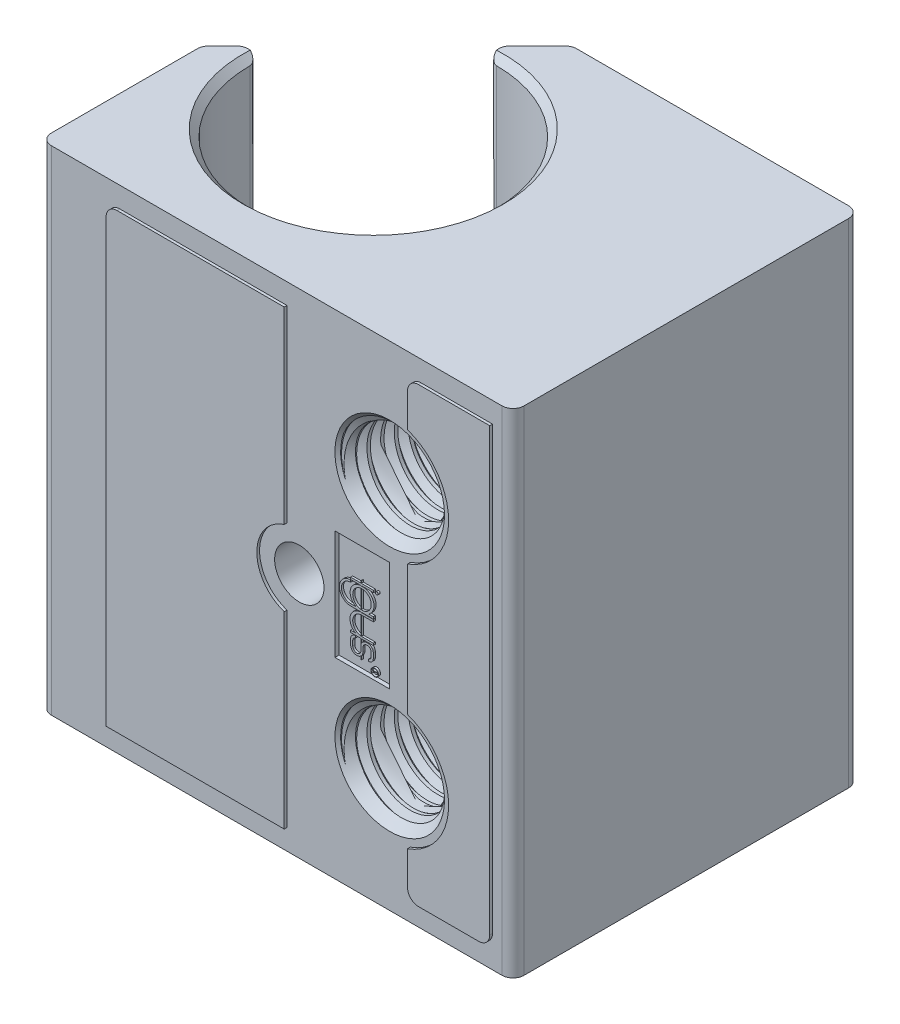
SolidWorks part; units mm, degrees
ref_plane "Front Plane" through (0, 0, 0) normal (0, 0, 1) x (1, 0, 0)
ref_plane "Top Plane" through (0, 0, 0) normal (0, 1, 0) x (1, 0, 0)
ref_plane "Right Plane" through (0, 0, 0) normal (1, 0, 0) x (0, 0, -1)
ref_plane "Plane1" through (0, 80.199, 0) normal (0, 1, 0) x (1, 0, 0)
sketch "Sketch1" plane through (0, 80.199, 0) normal (0, 1, 0) x (1, 0, 0)
  line L0 (28.5, 31) -> (28.5, 29.9861)
  line L1 (20.0139, 21.5) -> (19, 21.5)
  line L2 (19, 21.5) -> (17.5, 20)
  line L3 (17.5, 20) -> (17.5, 8.2)
  line L4 (17.5, 8.2) -> (52, 8.2)
  line L5 (52, 8.2) -> (52, 33.5)
  line L6 (52, 33.5) -> (31, 33.5)
  line L7 (31, 33.5) -> (28.5, 31)
  arc A0 (28.5, 29.9861) -> (20.0139, 21.5) centre (29, 21) cw
extrude "Boss-Extrude1" add sketch "Sketch1" against normal blind 16.2
sketch "Sketch2" plane through (0, 80.199, 0) normal (0, 1, 0) x (-1, 0, 0)
  line L0 (-28.5, -30.9875) -> (-28.5, -31)
  line L1 (-28.5, -31) -> (-31, -33.5)
  line L2 (-31, -33.5) -> (-52, -33.5)
  line L3 (-52, -33.5) -> (-52, -8.2)
  line L4 (-52, -8.2) -> (-17.5, -8.2)
  line L5 (-17.5, -8.2) -> (-17.5, -20)
  line L6 (-17.5, -20) -> (-19, -21.5)
  line L7 (-19, -21.5) -> (-19.0125, -21.5)
  arc A0 (-19.0125, -21.5) -> (-28.5, -30.9875) centre (-29, -21) ccw
extrude "Boss-Extrude2" add sketch "Sketch2" along normal blind 3.6
sketch "Sketch3" plane through (0, 83.799, 0) normal (0, 1, 0) x (-1, 0, 0)
  line L0 (-28.5, -21.5) -> (-28.5, -31)
  line L1 (-28.5, -31) -> (-31, -33.5)
  line L2 (-31, -33.5) -> (-52, -33.5)
  line L3 (-52, -33.5) -> (-52, -8.2)
  line L4 (-52, -8.2) -> (-17.5, -8.2)
  line L5 (-17.5, -8.2) -> (-17.5, -20)
  line L6 (-17.5, -20) -> (-19, -21.5)
  line L7 (-19, -21.5) -> (-28.5, -21.5)
extrude "Boss-Extrude3" add sketch "Sketch3" along normal blind 16.2
hole_wizard "Hole1" positions "Sketch5" profile "Sketch4" legacy
sketch "Sketch5" plane through (0, 83.799, 0) normal (0, -1, 0) x (-1, 0, 0)
  point P0 (-29, 21)
sketch "Sketch4" plane through (29, 83.799, -21) normal (1, 0, 0) x (0, 0, -1)
  line L0 (0, 0) -> (0, 16.2)
  line L1 (0, 16.2) -> (9, 16.2)
  line L2 (9, 16.2) -> (9, 0)
  line L3 (9, 0) -> (0, 0)
  line L4 (0, 110) -> (0, -10) construction
  dimension "Diameter" = 18
  dimension "Depth" = 16.2
sketch "Sketch6" plane through (0, 0, -8.2) normal (0, 0, 1) x (1, 0, 0)
  line L0 (44.5, 98.499) -> (50.5, 98.499)
  line L1 (50.5, 98.499) -> (50.5, 65.499)
  line L2 (50.5, 65.499) -> (44.5, 65.499)
  line L3 (44.5, 65.499) -> (44.5, 68.7564)
  line L4 (44.5, 77.2416) -> (44.5, 86.7564)
  line L5 (44.5, 95.2416) -> (44.5, 98.499)
  arc A0 (44.5, 68.7564) -> (44.5, 77.2416) centre (43, 72.999) ccw
  arc A1 (44.5, 86.7564) -> (44.5, 95.2416) centre (43, 90.999) ccw
extrude "Boss-Extrude4" add sketch "Sketch6" along normal blind 0.2
sketch "Sketch7" plane through (0, 0, -8.2) normal (0, 0, 1) x (1, 0, 0)
  line L0 (35.5, 65.499) -> (22.5, 65.499)
  line L1 (22.5, 65.499) -> (22.5, 98.499)
  line L2 (22.5, 98.499) -> (35.5, 98.499)
  line L3 (35.5, 98.499) -> (35.5, 84.7558)
  line L4 (35.5, 79.2422) -> (35.5, 65.499)
  arc A0 (35.5, 84.7558) -> (35.5, 79.2422) centre (36.4, 81.999) ccw
extrude "Boss-Extrude5" add sketch "Sketch7" along normal blind 0.2
sketch "Sketch8" plane through (0, 0, -8.2) normal (0, 0, 1) x (1, 0, 0)
  line L0 (39, 77.999) -> (43, 77.999)
  line L1 (43, 77.999) -> (43, 85.999)
  line L2 (43, 85.999) -> (39, 85.999)
  line L3 (39, 85.999) -> (39, 77.999)
extrude "Cut-Extrude1" cut sketch "Sketch8" against normal blind 0.3
sketch "Sketch9" plane through (0, 0, -8.5) normal (0, 0, 1) x (1, 0, 0)
  circle A0 centre (41.75, 78.349) radius 0.275
extrude "Boss-Extrude6" add sketch "Sketch9" along normal blind 0.15
hole_wizard "Hole2" positions "Sketch11" profile "Sketch10" legacy
sketch "Sketch11" plane through (0, 0, -8.35) normal (0, 0, 1) x (1, 0, 0)
  point P0 (41.75, 78.349)
sketch "Sketch10" plane through (41.75, 78.349, -8.35) normal (1, 0, 0) x (0, -1, 0)
  line L0 (0, 0) -> (0, 25.15)
  line L1 (0, 25.15) -> (0.25, 25.15)
  line L2 (0.25, 25.15) -> (0.25, 0)
  line L3 (0.25, 0) -> (0, 0)
  line L4 (0, 110) -> (0, -10) construction
  dimension "Diameter" = 0.5
  dimension "Depth" = 25.15
ref_plane "Plane2" through (0, 0, -8.5) normal (0, 0, -1) x (-1, 0, 0)
sketch "Sketch12" plane through (0, 0, -8.5) normal (0, 0, -1) x (-1, 0, 0)
  line L0 (-41.925, 78.424) -> (-41.925, 78.349)
  line L1 (-41.75, 78.349) -> (-41.75, 78.3615)
  line L2 (-41.75, 78.3615) -> (-41.575, 78.2615)
  line L3 (-41.575, 78.2615) -> (-41.5747, 78.3759)
  line L4 (-41.5747, 78.3759) -> (-41.75, 78.3759)
  line L5 (-41.75, 78.3759) -> (-41.75, 78.4115)
  line L6 (-41.75, 78.4115) -> (-41.575, 78.4115)
  line L7 (-41.575, 78.4115) -> (-41.575, 78.424)
  line L8 (-41.575, 78.424) -> (-41.925, 78.424)
  arc A0 (-41.925, 78.349) -> (-41.75, 78.349) centre (-41.8375, 78.349) ccw
extrude "Boss-Extrude7" add sketch "Sketch12" against normal blind 0.15
sketch "Sketch13" plane through (0, 0, -8.35) normal (0, 0, 1) x (1, 0, 0)
  line L0 (41.7625, 78.4115) -> (41.7625, 78.349)
  line L1 (41.9125, 78.349) -> (41.9125, 78.4115)
  line L2 (41.9125, 78.4115) -> (41.7625, 78.4115)
  arc A0 (41.7625, 78.349) -> (41.9125, 78.349) centre (41.8375, 78.349) ccw
extrude "Cut-Extrude2" cut sketch "Sketch13" against normal blind 0.15
sketch "Sketch14" plane through (0, 0, -8.5) normal (0, 0, 1) x (1, 0, 0)
  line L0 (41.65, 80.149) -> (41.65, 79.999)
  line L1 (41.65, 79.999) -> (40.775, 79.999)
  line L2 (40.775, 79.999) -> (40.775, 79.699)
  line L3 (41.65, 79.549) -> (41.65, 79.174)
  line L4 (41.3, 78.824) -> (41.3, 78.974)
  line L5 (41.5, 79.224) -> (41.5, 79.499)
  line L6 (40.9, 79.499) -> (40.9, 79.224)
  line L7 (40.775, 78.9128) -> (40.775, 78.649)
  line L8 (40.775, 78.649) -> (40.75, 78.649)
  line L9 (40.75, 78.649) -> (40.75, 78.8886)
  line L10 (40, 79.224) -> (40, 79.624)
  line L11 (40.35, 79.974) -> (40.35, 79.824)
  line L12 (40.15, 79.574) -> (40.15, 79.224)
  line L13 (40.75, 79.224) -> (40.75, 79.999)
  line L14 (40.75, 79.999) -> (40, 79.999)
  line L15 (40, 79.999) -> (40, 80.149)
  line L16 (40, 80.149) -> (40.35, 80.149)
  line L17 (40.75, 81.649) -> (40.75, 81.674)
  line L18 (40.75, 81.674) -> (40, 81.674)
  line L19 (40, 83.324) -> (40, 83.174)
  line L20 (40, 81.824) -> (40.4, 81.824)
  line L21 (40.75, 83.324) -> (40.75, 83.349)
  line L22 (40.75, 83.349) -> (40, 83.349)
  line L23 (40, 83.349) -> (40, 83.499)
  line L24 (40, 83.499) -> (40.75, 83.499)
  line L25 (40.75, 83.499) -> (40.75, 83.649)
  line L26 (40.75, 83.649) -> (40.775, 83.649)
  line L27 (40.775, 83.649) -> (40.775, 83.499)
  line L28 (40.775, 83.499) -> (41.675, 83.499)
  line L29 (41.675, 83.499) -> (41.675, 83.349)
  line L30 (41.675, 83.349) -> (40.8, 83.349)
  line L31 (40.8, 83.349) -> (40.8, 83.324)
  line L32 (41.3, 81.824) -> (41.65, 81.824)
  line L33 (41.65, 81.824) -> (41.65, 81.674)
  line L34 (41.65, 81.674) -> (40.775, 81.674)
  line L35 (40.775, 81.674) -> (40.775, 81.649)
  line L36 (40.775, 81.649) -> (41.65, 81.649)
  line L37 (41.65, 81.649) -> (41.65, 81.499)
  line L38 (41.65, 81.499) -> (40.775, 81.499)
  line L39 (40.775, 81.499) -> (40.775, 80.1508)
  line L40 (40.825, 80.149) -> (41.65, 80.149)
  arc A0 (40.775, 79.699) -> (41.2, 79.949) centre (41.2, 79.4627) cw
  arc A1 (41.2, 79.949) -> (41.65, 79.549) centre (41.2472, 79.549) cw
  arc A2 (41.65, 79.174) -> (41.3, 78.824) centre (41.3, 79.174) cw
  arc A3 (41.3, 78.974) -> (41.5, 79.224) centre (41.2438, 79.224) ccw
  arc A4 (41.5, 79.499) -> (40.9, 79.499) centre (41.2, 79.499) ccw
  arc A5 (40.9, 79.224) -> (40.775, 78.9128) centre (40.45, 79.224) cw
  arc A6 (40.75, 78.8886) -> (40, 79.224) centre (40.45, 79.224) cw
  arc A7 (40, 79.624) -> (40.35, 79.974) centre (40.35, 79.624) cw
  arc A8 (40.35, 79.824) -> (40.15, 79.574) centre (40.4062, 79.574) ccw
  arc A9 (40.15, 79.224) -> (40.75, 79.224) centre (40.45, 79.224) ccw
  arc A10 (40.35, 80.149) -> (40.75, 81.649) centre (40.75, 80.8457) cw
  arc A11 (40, 81.674) -> (40, 83.324) centre (40, 82.499) cw
  arc A12 (40, 83.174) -> (40, 81.824) centre (40, 82.499) ccw
  arc A13 (40.4, 81.824) -> (40.75, 83.324) centre (40.75, 82.5332) cw
  arc A14 (40.8, 83.324) -> (41.3, 81.824) centre (40.8965, 82.5228) cw
  arc A15 (40.775, 80.1508) -> (40.825, 80.149) centre (40.825, 80.8261) ccw
extrude "Boss-Extrude8" add sketch "Sketch14" along normal blind 0.15
sketch "Sketch15" plane through (0, 0, -8.35) normal (0, 0, 1) x (1, 0, 0)
  line L0 (40.75, 80.1532) -> (40.75, 81.499)
  arc A0 (40.75, 81.499) -> (40.75, 80.1532) centre (40.825, 80.8261) ccw
extrude "Cut-Extrude3" cut sketch "Sketch15" against normal blind 0.15
sketch "Sketch16" plane through (0, 0, -8.35) normal (0, 0, 1) x (1, 0, 0)
  line L0 (40.75, 81.8282) -> (40.75, 83.1698)
  arc A0 (40.75, 83.1698) -> (40.75, 81.8282) centre (40.825, 82.499) ccw
extrude "Cut-Extrude4" cut sketch "Sketch16" against normal blind 0.15
sketch "Sketch17" plane through (0, 0, -8.35) normal (0, 0, 1) x (1, 0, 0)
  line L0 (40.775, 83.1721) -> (40.775, 81.8259)
  arc A0 (40.775, 81.8259) -> (40.775, 83.1721) centre (40.825, 82.499) ccw
extrude "Cut-Extrude5" cut sketch "Sketch17" against normal blind 0.15
draft "Draft1" type of draft neutral plane draft angle 29.745 faces to draft 1 face at (41.6624, 78.3759, -8.425) neutral plane through (41.75, 78.3759, -8.35) neutral plane normal (-1, 0, 0) parameters "D1"=29.745
ref_plane "Plane3" through (0, 83.424, 0) normal (0, -1, 0) x (1, 0, 0)
sketch "Sketch18" plane through (0, 83.424, 0) normal (0, -1, 0) x (1, 0, 0)
  line L0 (42, -8.35) -> (41.9, -8.35)
  line L1 (41.9, -8.35) -> (41.9, -8.5)
  line L2 (41.9, -8.5) -> (42, -8.5)
  line L3 (42, -8.5) -> (42, -8.35)
  line L4 (41.9, -8.35) -> (41.9, -8.5) construction
revolve "Revolve1" add sketch "Sketch18" angle 360 about L4 reverse direction yes
hole_wizard "Hole3" positions "Sketch20" profile "Sketch19" legacy
sketch "Sketch20" plane through (0, 0, -33.5) normal (0, 0, -1) x (-1, 0, 0)
  point P0 (-43, 72.999)
  point P1 (-43, 90.999)
sketch "Sketch19" plane through (43, 72.999, -33.5) normal (1, 0, 0) x (0, 1, 0)
  line L0 (0, 0) -> (0, 25.301)
  line L1 (0, 25.301) -> (3.25, 25.301)
  line L2 (3.25, 25.301) -> (3.25, 4)
  line L3 (3.25, 4) -> (6.5, 4)
  line L4 (6.5, 4) -> (6.5, 0)
  line L5 (6.5, 0) -> (0, 0)
  line L6 (0, 110) -> (0, -10) construction
  dimension "Diameter" = 6.5
  dimension "Depth" = 25.301
  dimension "C-Bore Diameter" = 13
  dimension "C-Bore Depth" = 4
hole_wizard "#5 Clearance Hole1" positions "Sketch22" profile "Sketch21" hole size "#5" standard "ANSI Inch"
sketch "Sketch22" plane through (0, 0, -8.2) normal (0, 0, 1) x (1, 0, 0)
  point P0 (36.4, 81.999)
sketch "Sketch21" plane through (36.4, 81.999, -8.2) normal (1, 0, 0) x (0, -1, 0)
  line L0 (0, 0) -> (0, 12.8)
  line L1 (0, 12.8) -> (1.8, 12.8)
  line L2 (1.8, 12.8) -> (1.8, 0)
  line L5 (1.8, 0) -> (0, 0)
  line L11 (0, -6.35) -> (0, 107.95) construction
  dimension "Thru Hole Dia." = 3.6
  dimension "Thru Hole Depth" = 12.8
chamfer "Chamfer1" distance 0.75 angle 45 4 edges at (46.25, 72.999, -8.2) (46.25, 90.999, -8.2) (39.75, 72.999, -29.5) (39.75, 90.999, -29.5)
chamfer "Chamfer2" distance 0.5 angle 45 2 edges at (35.364, 63.999, -14.636) (35.364, 99.999, -14.636)
fillet "Fillet1" radius 0.5 4 edges at (28.5, 91.649, -29.9861) (20.0139, 91.649, -21.5) (28.5, 72.349, -29.9861) (20.0139, 72.349, -21.5) tangent propagation no
fillet "Fillet2" radius 0.8 11 edges at (22.5, 98.499, -8.1) (50.5, 65.499, -8.1) (44.5, 98.499, -8.1) (19, 81.999, -21.5) (17.5, 81.999, -8.2) (17.5, 81.999, -20) (28.5, 81.999, -31) (52, 81.999, -8.2) (44.5, 65.499, -8.1) (52, 81.999, -33.5) (31, 81.999, -33.5) tangent propagation no
thread "Thread1" pitch 1 method cut profile "Thread Profile1" start angle 0, offset 2.54, length 0, pitch 1, diameter 6.5
ref_plane "Plane4" through (46.25, 72.999, -31.29) normal (0, -1, 0) x (1, 0, 0)
sketch "Thread Profile1" plane through (46.25, 72.999, -31.29) normal (0, -1, 0) x (1, 0, 0)
  line L0 (0, 0) -> (0, 1) construction
  line L1 (0, 0) -> (0.5413, 0.3125)
  line L2 (0.5413, 0.3125) -> (0.5413, 0.4375)
  line L3 (0.5413, 0.4375) -> (0, 0.75)
  line L4 (0.5413, 0.375) -> (0, 0.375) construction
  line L11 (0, 0) -> (0, 0.75)
  point P2 (0, 0)
  dimension "Pitch" = 1
  dimension "Profile_Angle" = 60
  dimension "Profile_Land" = 0.125
  dimension "Profile_Height" = 0.5413
thread "Thread2" pitch 1 method cut profile "Thread Profile2" start angle 0, offset 2.54, length 0, pitch 1, diameter 6.5
ref_plane "Plane5" through (46.25, 90.999, -31.29) normal (0, -1, 0) x (1, 0, 0)
sketch "Thread Profile2" plane through (46.25, 90.999, -31.29) normal (0, -1, 0) x (1, 0, 0)
  line L0 (0, 0) -> (0, 1) construction
  line L1 (0, 0) -> (0.5413, 0.3125)
  line L2 (0.5413, 0.3125) -> (0.5413, 0.4375)
  line L3 (0.5413, 0.4375) -> (0, 0.75)
  line L4 (0.5413, 0.375) -> (0, 0.375) construction
  line L11 (0, 0) -> (0, 0.75)
  point P2 (0, 0)
  dimension "Pitch" = 1
  dimension "Profile_Angle" = 60
  dimension "Profile_Land" = 0.125
  dimension "Profile_Height" = 0.5413
